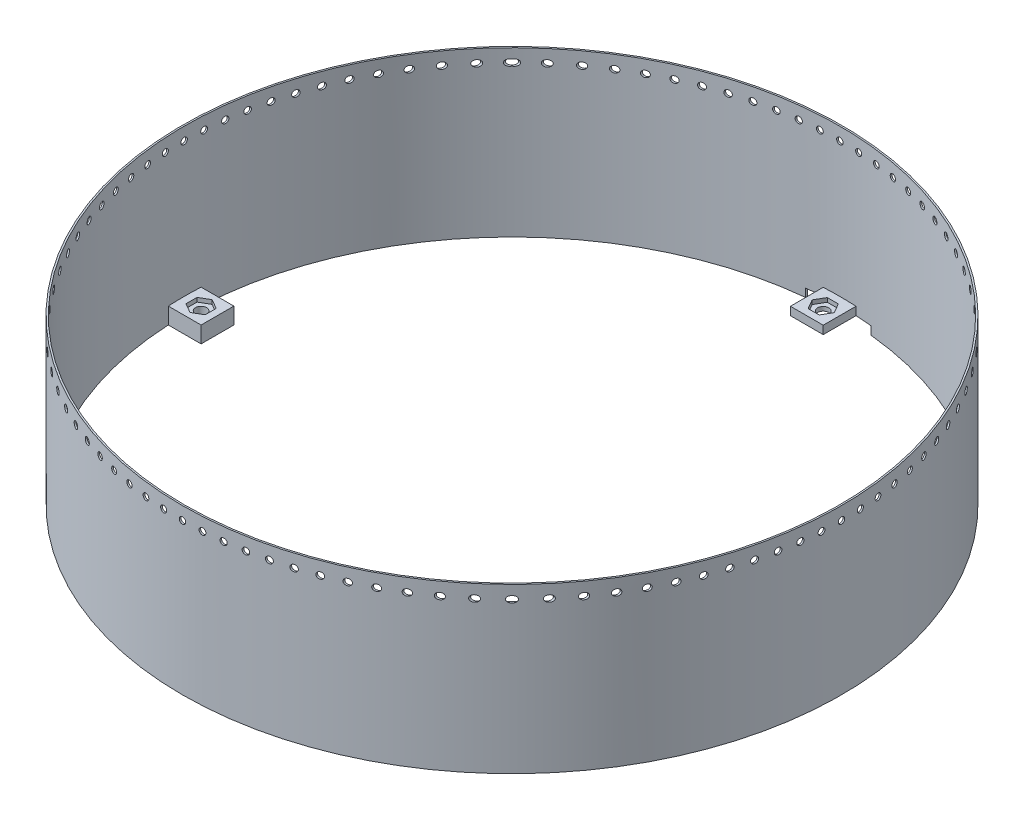
SolidWorks part; units mm, degrees
ref_plane "Front Plane" through (0, 0, 0) normal (0, 0, 1) x (1, 0, 0)
ref_plane "Top Plane" through (0, 0, 0) normal (0, 1, 0) x (1, 0, 0)
ref_plane "Right Plane" through (0, 0, 0) normal (1, 0, 0) x (0, 0, -1)
sketch "Sketch1" plane through (0, 0, 0) normal (0, 1, 0) x (1, 0, 0)
  circle A0 centre (0, 0) radius 127.635
  circle A1 centre (0, 0) radius 127
  dimension "D1" = 254
  dimension "D2" = 255.27
extrude "Boss-Extrude1" add sketch "Sketch1" against normal blind 63.5
ref_axis "Axis1" through (0, -63.5, 0) along (0, 1, 0)
ref_plane "Plane1" through (0, 0, 127.635) normal (0, 0, 1) x (1, 0, 0)
sketch "Sketch3" plane through (0, 0, 0) normal (0, 1, 0) x (1, 0, 0)
  line L0 (0, 0) -> (89.8026, 89.8026)
  line L1 (0, 0) -> (89.8026, -89.8026)
  line L2 (0, 0) -> (-89.8026, -89.8026)
  line L3 (0, 0) -> (-89.8026, 89.8026)
  line L4 (-34.925, -127.635) -> (34.925, -127.635) construction
  circle A0 centre (0, 0) radius 127 construction
  dimension "D1" = 90
  dimension "D2" = 45
sketch "Sketch2" plane through (0, 0, 127.635) normal (0, 0, 1) x (1, 0, 0)
  line L0 (0, -63.5) -> (0, 0) construction
  line L1 (0, 0) -> (0, -24.8295) construction
  line L2 (-89.8026, 0) -> (-89.8026, -63.5) construction
  line L3 (0, 0) -> (-89.8026, 0) construction
  line L4 (0, 0) -> (-89.8026, 0) construction
  line L5 (-127.635, -63.5) -> (127.635, -63.5) construction
  line L6 (89.8026, 0) -> (89.8026, -63.5) construction
  line L7 (0, 0) -> (89.8026, 0) construction
  circle A0 centre (0, -5) radius 1.25
  circle A75 centre (7.5184, -5) radius 1.25
  circle A76 centre (15.0368, -5) radius 1.25
  circle A77 centre (22.5552, -5) radius 1.25
  circle A78 centre (30.0736, -5) radius 1.25
  circle A79 centre (37.592, -5) radius 1.25
  circle A80 centre (45.1104, -5) radius 1.25
  circle A81 centre (52.6288, -5) radius 1.25
  circle A82 centre (60.1472, -5) radius 1.25
  circle A83 centre (67.6656, -5) radius 1.25
  circle A84 centre (75.184, -5) radius 1.25
  circle A85 centre (82.7024, -5) radius 1.25
  circle A86 centre (90.2208, -5) radius 1.25
  circle A87 centre (-90.2208, -5) radius 1.25
  circle A88 centre (-82.7024, -5) radius 1.25
  circle A89 centre (-75.184, -5) radius 1.25
  circle A90 centre (-67.6656, -5) radius 1.25
  circle A91 centre (-60.1472, -5) radius 1.25
  circle A92 centre (-52.6288, -5) radius 1.25
  circle A93 centre (-45.1104, -5) radius 1.25
  circle A94 centre (-37.592, -5) radius 1.25
  circle A95 centre (-30.0736, -5) radius 1.25
  circle A96 centre (-22.5552, -5) radius 1.25
  circle A97 centre (-15.0368, -5) radius 1.25
  circle A98 centre (-7.5184, -5) radius 1.25
  dimension "D1" = 13
extrude "Cut-Extrude1" cut sketch "Sketch2" against normal through all
pattern_circular "CirPattern1" count 2 every 90 about axis through (0, -63.5, 0) along (0, 1, 0) of "Cut-Extrude1"
ref_plane "Plane3" through (0, -63.5, 0) normal (0, -1, 0) x (-1, 0, 0)
sketch "Sketch4" plane through (0, -63.5, 0) normal (0, -1, 0) x (-1, 0, 0)
  line L0 (-6.291, -126.8441) -> (-6.291, -114.1382)
  line L1 (-6.291, -114.1382) -> (6.409, -114.1382)
  line L2 (6.409, -114.1382) -> (6.409, -126.8382)
  line L3 (0.059, -114.1382) -> (0.059, -125.8807) construction
  line L4 (6.409, -120.4882) -> (-5.265, -120.4882) construction
  line L5 (-114.1382, 6.291) -> (-114.1382, -6.409)
  line L6 (-126.8441, 6.291) -> (-114.1382, 6.291)
  line L7 (-114.1382, -6.409) -> (-126.8382, -6.409)
  line L8 (6.291, 114.1382) -> (-6.409, 114.1382)
  line L9 (6.291, 126.8441) -> (6.291, 114.1382)
  line L10 (-6.409, 114.1382) -> (-6.409, 126.8382)
  line L11 (114.1382, -6.291) -> (114.1382, 6.409)
  line L12 (126.8441, -6.291) -> (114.1382, -6.291)
  line L13 (114.1382, 6.409) -> (126.8382, 6.409)
  circle A0 centre (0, 0) radius 127 construction
  circle A1 centre (0, 0) radius 127
  circle A2 centre (0.059, -120.4882) radius 2.159
  circle A3 centre (0, 0) radius 127
  circle A4 centre (-120.4882, -0.059) radius 2.159
  circle A5 centre (0, 0) radius 127
  circle A6 centre (-0.059, 120.4882) radius 2.159
  circle A7 centre (0, 0) radius 127
  circle A8 centre (120.4882, 0.059) radius 2.159
  point P37 (0, 0)
  dimension "D3" = 4.318
  dimension "D1" = 12.7
  dimension "D2" = 12.7
  dimension "D4" = 4
extrude "Boss-Extrude2" add sketch "Sketch4" against normal blind 6.35 contours L0 A1 L2 L1 A2 | L12 A1 L13 L11 A8 | L9 A1 L10 L8 A6 | L6 A1 L7 L5 A4 region at (6.1102, -63.5, 120.4911) region at (126.8192, -63.5, 0.059) region at (-120.4911, -63.5, 6.1102) region at (0.059, -63.5, -126.8192)
sketch "Sketch5" plane through (0, -57.15, 0) normal (0, 1, 0) x (1, 0, 0)
  line L0 (-116.7767, -2.0838) -> (-116.7767, 2.2018)
  line L1 (2.0838, -116.7767) -> (-2.2018, -116.7767)
  line L2 (-2.2018, -116.7767) -> (-4.3447, -120.4882)
  line L3 (6.291, -126.8441) -> (6.291, -114.1382)
  line L4 (6.291, -114.1382) -> (-6.409, -114.1382)
  line L5 (-6.409, -114.1382) -> (-6.409, -126.8382)
  line L6 (6.291, -126.8441) -> (6.291, -114.1382)
  line L7 (6.291, -114.1382) -> (-6.409, -114.1382)
  line L8 (-6.409, -114.1382) -> (-6.409, -126.8382)
  line L9 (-4.3447, -120.4882) -> (-2.2018, -124.1997)
  line L10 (-2.2018, -124.1997) -> (2.0838, -124.1997)
  line L11 (2.0838, -124.1997) -> (4.2267, -120.4882)
  line L12 (4.2267, -120.4882) -> (2.0838, -116.7767)
  line L13 (-116.7767, 2.2018) -> (-120.4882, 4.3447)
  line L14 (-120.4882, 4.3447) -> (-124.1997, 2.2018)
  line L15 (-124.1997, 2.2018) -> (-124.1997, -2.0838)
  line L16 (-124.1997, -2.0838) -> (-120.4882, -4.2267)
  line L17 (-120.4882, -4.2267) -> (-116.7767, -2.0838)
  line L18 (-2.0838, 116.7767) -> (2.2018, 116.7767)
  line L19 (2.2018, 116.7767) -> (4.3447, 120.4882)
  line L20 (4.3447, 120.4882) -> (2.2018, 124.1997)
  line L21 (2.2018, 124.1997) -> (-2.0838, 124.1997)
  line L22 (-2.0838, 124.1997) -> (-4.2267, 120.4882)
  line L23 (-4.2267, 120.4882) -> (-2.0838, 116.7767)
  line L24 (116.7767, 2.0838) -> (116.7767, -2.2018)
  line L25 (116.7767, -2.2018) -> (120.4882, -4.3447)
  line L26 (120.4882, -4.3447) -> (124.1997, -2.2018)
  line L27 (124.1997, -2.2018) -> (124.1997, 2.0838)
  line L28 (124.1997, 2.0838) -> (120.4882, 4.2267)
  line L29 (120.4882, 4.2267) -> (116.7767, 2.0838)
  circle A0 centre (-0.059, -120.4882) radius 2.159 construction
  arc A1 (-6.409, -126.8382) -> (6.291, -126.8441) centre (0, 0) ccw
  arc A2 (-6.409, -126.8382) -> (6.291, -126.8441) centre (0, 0) ccw
  circle A3 centre (-0.059, -120.4882) radius 2.159 construction
  circle A4 centre (-0.059, -120.4882) radius 3.7115 construction
  point P36 (0, 0)
  circle M12 centre (-0.059, -120.4882) radius 2.159
  dimension "D1" = 0
  dimension "D2" = 4
extrude "Cut-Extrude2" cut sketch "Sketch5" against normal blind 1.5875 contours L11 L12 L1 L2 L9 L10 M12 | L28 L29 L24 L25 L26 L27 | L22 L23 L18 L19 L20 L21 | L16 L17 L0 L13 L14 L15 region at (-120.4882, -57.15, -0.059) region at (3.057, -57.15, 118.6891) region at (0.059, -57.15, -120.4882) region at (120.4882, -57.15, 0.059)
sketch "Sketch6" plane through (0, 0, -114.1382) normal (0, 0, 1) x (1, 0, 0)
  line L0 (-127.635, -63.5) -> (127.635, -63.5) construction
  line L4 (-6.291, -63.5) -> (6.409, -63.5)
  line L5 (6.409, -63.5) -> (6.409, -57.15)
  line L6 (6.409, -57.15) -> (-6.291, -57.15)
  line L7 (-6.291, -57.15) -> (-6.291, -63.5)
  line L9 (6.409, -63.5) -> (6.409, -57.15)
  line L10 (6.409, -57.15) -> (-6.291, -57.15)
  line L11 (-6.291, -57.15) -> (-6.291, -63.5)
  line L13 (-12.641, -63.5) -> (12.759, -63.5)
  line L14 (-12.641, -63.5) -> (-12.641, -60.325)
  line L15 (-12.641, -60.325) -> (12.759, -60.325)
  line L16 (12.759, -63.5) -> (12.759, -60.325)
  point P10 (0.059, -60.325)
  point P11 (0.059, -57.15)
  line M5 (-6.291, -63.5) -> (6.409, -63.5)
  line M6 (6.409, -63.5) -> (6.409, -57.15)
  line M8 (-6.291, -57.15) -> (-6.291, -63.5)
  dimension "D2" = 25.4
  dimension "D3" = 3.175
  dimension "D1" = 0
extrude "Cut-Extrude3" cut sketch "Sketch6" against normal through all contours M8 M5 M6 | L15 L14 L13 L11 | L13 L16 L15 M6 region at (0.059, -61.9125, -114.1382) region at (-9.466, -61.9125, -114.1382) region at (9.584, -61.9125, -114.1382)
